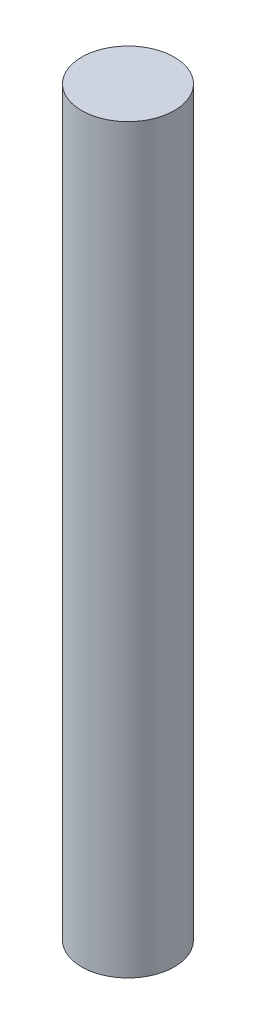
SolidWorks part; units mm, degrees
ref_plane "Front Plane" through (0, 0, 0) normal (0, 0, 1) x (1, 0, 0)
ref_plane "Top Plane" through (0, 0, 0) normal (0, 1, 0) x (1, 0, 0)
ref_plane "Right Plane" through (0, 0, 0) normal (1, 0, 0) x (0, 0, -1)
sketch "Sketch1" plane through (0, 0, 0) normal (0, 1, 0) x (1, 0, 0)
  circle A0 centre (0, 0) radius 5
  dimension "D1" = 10
extrude "Boss-Extrude1" add sketch "Sketch1" along normal blind 40 and the other way blind 40
